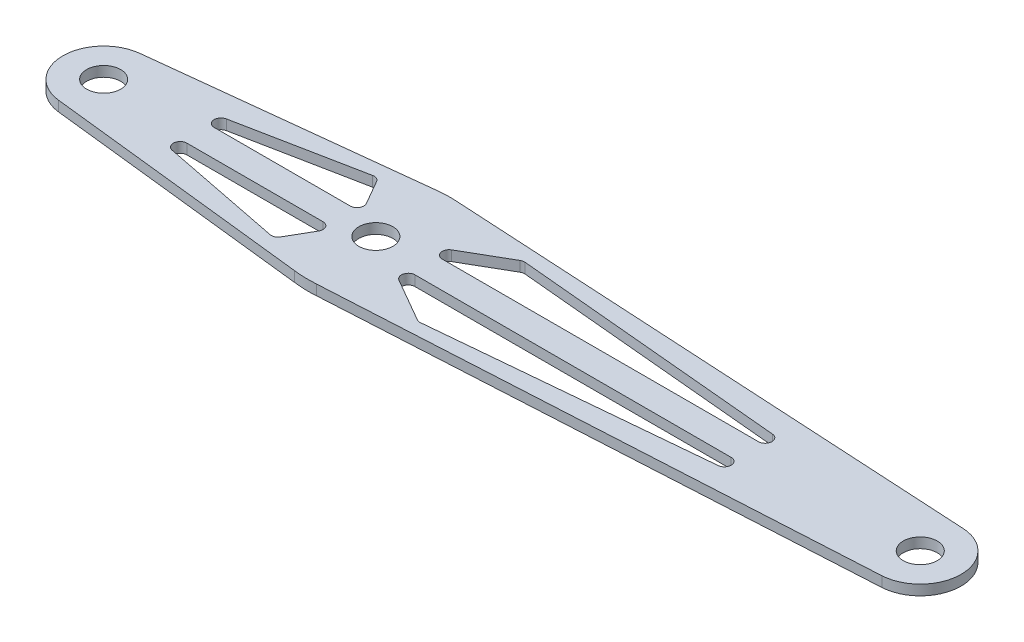
SolidWorks part; units mm, degrees
ref_plane "前视基准面" through (0, 0, 0) normal (0, 0, 1) x (1, 0, 0)
ref_plane "上视基准面" through (0, 0, 0) normal (0, 1, 0) x (1, 0, 0)
ref_plane "右视基准面" through (0, 0, 0) normal (1, 0, 0) x (0, 0, -1)
other "Configuration Table"
sketch "草图1" plane through (0, 0, 0) normal (0, 1, 0) x (1, 0, 0)
  line L0 (-96.1987, 0) -> (0, 0) construction
  line L1 (0, 0) -> (80, 0) construction
  line L2 (80, 0) -> (240, 0) construction
  line L3 (-1.3306, 11.926) -> (80, 21)
  line L4 (80, 21) -> (240.6725, 11.9811)
  line L5 (-1.3306, -11.926) -> (80, -21)
  line L6 (80, -21) -> (240.6725, -11.9811)
  circle A0 centre (0, 0) radius 5
  circle A1 centre (80, 0) radius 5
  circle A2 centre (240, 0) radius 5
  arc A3 (-1.3306, -11.926) -> (-1.3306, 11.926) centre (0, 0) cw
  arc A4 (240.6725, 11.9811) -> (240.6725, -11.9811) centre (240, 0) cw
  point P8 (80, 40.7077)
  point P13 (77.5983, -39.5312)
  point P16 (80, 51.4279)
  point P17 (80, -61.9462)
  point P18 (80, 26.739)
  dimension "D1" = 10
  dimension "D2" = 10
  dimension "D3" = 10
  dimension "D4" = 80
  dimension "D6" = 12
  dimension "D7" = 12
  dimension "D8" = 42
  dimension "D5" = 160
extrude "凸台-拉伸1" add sketch "草图1" along normal blind 3
fillet "圆角1" radius 40 2 edges at (80, 1.5, 21) (80, 1.5, -21) curvature continuous yes
sketch "草图2" plane through (0, 0, 0) normal (0, -1, 0) x (1, 0, 0)
  line L0 (240.8967, 15.9749) -> (83.5704, 24.8059) construction
  line L1 (76.2257, 24.6037) -> (-1.7741, 15.9013) construction
  line L2 (-1.7741, -15.9013) -> (76.2257, -24.6037) construction
  line L3 (83.5704, -24.8059) -> (240.8967, -15.9749) construction
  line L4 (240.6725, 11.9811) -> (83.3462, 20.8122)
  line L5 (76.6692, 20.6284) -> (-1.3306, 11.926)
  line L6 (-1.3306, -11.926) -> (76.6692, -20.6284)
  line L7 (83.3462, -20.8122) -> (240.6725, -11.9811)
  line L8 (240.6725, 11.9811) -> (83.3462, 20.8122) construction
  line L9 (76.6692, 20.6284) -> (-1.3306, 11.926) construction
  line L10 (-1.3306, -11.926) -> (76.6692, -20.6284) construction
  line L11 (83.3462, -20.8122) -> (240.6725, -11.9811) construction
  line L12 (83.122, -16.8185) -> (240.4483, -7.9874) construction
  line L13 (240.4483, 7.9874) -> (83.122, 16.8185) construction
  line L14 (77.1127, 16.6531) -> (-0.8871, 7.9507) construction
  line L15 (-0.8871, -7.9507) -> (77.1127, -16.6531) construction
  line L16 (-28.9871, 0) -> (305.3613, 0) construction
  line L17 (-28.9871, -4) -> (305.3613, -4) construction
  line L18 (-28.9871, 4) -> (305.3613, 4) construction
  line L19 (8.0623, 4) -> (65.3878, 15.3449)
  line L20 (65.3878, 15.3449) -> (71.9377, 4)
  line L21 (71.9377, 4) -> (8.0623, 4)
  line L22 (88.0623, 4) -> (107.8594, 15.4299)
  line L23 (107.8594, 15.4299) -> (231.9377, 4)
  line L24 (231.9377, 4) -> (88.0623, 4)
  line L25 (107.8594, -15.4299) -> (231.9377, -4)
  line L26 (88.0623, -4) -> (107.8594, -15.4299)
  line L27 (231.9377, -4) -> (88.0623, -4)
  line L28 (65.3878, -15.3449) -> (71.9377, -4)
  line L29 (8.0623, -4) -> (65.3878, -15.3449)
  line L30 (71.9377, -4) -> (8.0623, -4)
  circle A0 centre (240, 0) radius 5 construction
  circle A1 centre (80, 0) radius 5 construction
  arc A2 (-1.3306, 11.926) -> (-1.3306, -11.926) centre (0, 0) ccw
  arc A3 (240.6725, -11.9811) -> (240.6725, 11.9811) centre (240, 0) ccw
  arc A4 (-1.3306, 11.926) -> (-1.3306, -11.926) centre (0, 0) ccw construction
  arc A5 (240.6725, -11.9811) -> (240.6725, 11.9811) centre (240, 0) ccw construction
  circle A6 centre (0, 0) radius 5 construction
  circle A7 centre (240, 0) radius 5 construction
  circle A8 centre (80, 0) radius 5 construction
  circle A9 centre (0, 0) radius 5 construction
  arc A10 (-1.7741, 15.9013) -> (-1.7741, -15.9013) centre (0, 0) ccw construction
  circle A11 centre (240, 0) radius 9 construction
  circle A12 centre (80, 0) radius 9 construction
  circle A13 centre (0, 0) radius 9 construction
  arc A14 (240.4483, -7.9874) -> (240.4483, 7.9874) centre (240, 0) ccw construction
  arc A15 (-0.8871, 7.9507) -> (-0.8871, -7.9507) centre (0, 0) ccw construction
  arc A16 (240.8967, -15.9749) -> (240.8967, 15.9749) centre (240, 0) ccw construction
  spline S0 degree 1 poles (83.5704, 24.8059) (76.2257, 24.6037) knots 0 0 1 1 construction
  spline S1 degree 1 poles (76.2257, -24.6037) (83.5704, -24.8059) knots 0 0 1 1 construction
  spline S2 degree 2 poles (3072.0697, -237.9003) (127.5725, 19.5203) (81.6761, 20.8903) (80.7944, 20.9167) (80.0042, 20.895) (79.2143, 20.8733) (78.3339, 20.7984) (32.6608, 16.9155) (-2893.3663, -402.0343) knots -19.097283 -19.097283 -19.097283 0.25 0.25 0.5 0.5 0.75 0.75 20.066224 20.066224 20.066224 only from (83.3462, 20.8122) to (76.6692, 20.6284)
  spline S3 degree 2 poles (-2893.2975, 402.0989) (32.5809, -16.9056) (78.3325, -20.7983) (79.2114, -20.8731) (80.0016, -20.8949) (80.7914, -20.9167) (81.6746, -20.8904) (127.4922, -19.5258) (3072.1349, 237.8321) knots -19.097283 -19.097283 -19.097283 0.25 0.25 0.5 0.5 0.75 0.75 20.066224 20.066224 20.066224 only from (76.6692, -20.6284) to (83.3462, -20.8122)
  spline S4 degree 2 poles (83.3462, 20.8122) (82.2692, 20.8726) (81.6761, 20.8903) (80.7944, 20.9167) (80.0042, 20.895) (79.2143, 20.8733) (78.3339, 20.7984) (77.7428, 20.7482) (76.6692, 20.6284) knots 0 0 0 0.25 0.25 0.5 0.5 0.75 0.75 1 1 1 construction
  spline S5 degree 2 poles (76.6692, -20.6284) (77.7413, -20.748) (78.3325, -20.7983) (79.2114, -20.8731) (80.0016, -20.8949) (80.7914, -20.9167) (81.6746, -20.8904) (82.2676, -20.8727) (83.3462, -20.8122) knots 0 0 0 0.25 0.25 0.5 0.5 0.75 0.75 1 1 1 construction
  spline S6 degree 2 poles (83.5704, 24.8059) (82.8804, 24.8447) (82.2083, 24.874) (81.9692, 24.883) (81.8077, 24.8883) (81.5481, 24.8953) (81.2475, 24.9013) (80.7068, 24.9067) (79.8943, 24.8971) (79.0822, 24.862) (78.5422, 24.827) (78.2421, 24.8045) (77.9828, 24.7832) (77.8219, 24.7689) (77.5834, 24.7468) (76.9134, 24.6805) (76.2257, 24.6037) knots 0 0 0 0.15625 0.203125 0.234375 0.265625 0.296875 0.34375 0.4375 0.5625 0.65625 0.703125 0.734375 0.765625 0.796875 0.84375 1 1 1 construction
  spline S7 degree 2 poles (76.2257, -24.6037) (76.9125, -24.6804) (77.5819, -24.7467) (77.8202, -24.7688) (77.9811, -24.783) (78.24, -24.8043) (78.5398, -24.8268) (79.0794, -24.8619) (79.8912, -24.897) (80.7039, -24.9067) (81.2451, -24.9014) (81.546, -24.8954) (81.806, -24.8884) (81.9675, -24.883) (82.2069, -24.8741) (82.8794, -24.8447) (83.5704, -24.8059) knots 0 0 0 0.15625 0.203125 0.234375 0.265625 0.296875 0.34375 0.4375 0.5625 0.65625 0.703125 0.734375 0.765625 0.796875 0.84375 1 1 1 construction
  spline S8 degree 1 poles (83.122, 16.8185) (77.1127, 16.6531) knots 0 0 1 1 construction
  spline S9 degree 2 poles (83.122, 16.8185) (82.7287, 16.8405) (82.1945, 16.867) (81.8809, 16.8807) (81.6863, 16.888) (81.5677, 16.8919) (81.3613, 16.8975) (81.1273, 16.9021) (80.7114, 16.9062) (80.1138, 16.8991) (79.5172, 16.8734) (79.1018, 16.8465) (78.868, 16.8289) (78.6617, 16.812) (78.5437, 16.8015) (78.3498, 16.7836) (78.0372, 16.7527) (77.5048, 16.6968) (77.1127, 16.6531) knots 0 0 0 0.09375 0.15625 0.203125 0.234375 0.265625 0.296875 0.34375 0.4375 0.5625 0.65625 0.703125 0.734375 0.765625 0.796875 0.84375 0.90625 1 1 1 construction
  spline S10 degree 1 poles (77.1127, -16.6531) (83.122, -16.8185) knots 0 0 1 1 construction
  spline S11 degree 2 poles (77.1127, -16.6531) (77.5042, -16.6967) (78.0361, -16.7525) (78.3485, -16.7834) (78.5424, -16.8014) (78.6606, -16.8119) (78.8664, -16.8288) (79.0999, -16.8463) (79.5148, -16.8733) (80.112, -16.8991) (80.7091, -16.9062) (81.1254, -16.9022) (81.3598, -16.8975) (81.5666, -16.8919) (81.685, -16.888) (81.8796, -16.8807) (82.1934, -16.8671) (82.7282, -16.8406) (83.122, -16.8185) knots 0 0 0 0.09375 0.15625 0.203125 0.234375 0.265625 0.296875 0.34375 0.4375 0.5625 0.65625 0.703125 0.734375 0.765625 0.796875 0.84375 0.90625 1 1 1 construction
  point P55 (113.2075, 15.3449)
  point P60 (111.2291, 15.3449)
  point P61 (0, 0)
  point P62 (107.8594, 15.3449)
  point P63 (0, 0)
  dimension "D2" = 4
  dimension "D3" = 4
  dimension "D6" = 4
  dimension "D4" = 4
  dimension "D8" = 60
  dimension "D9" = 30
  dimension "D1" = 0
  dimension "D5" = 4
  dimension "D7" = 4
extrude "切除-拉伸1" cut sketch "草图2" against normal up to surface (3 mm away) up to face at (99.9216, 3, -0.0069)
fillet "圆角2" radius 2 12 edges at (65.3878, 1.5, -15.3449) (71.9377, 1.5, -4) (71.9377, 1.5, 4) (8.0623, 1.5, 4) (8.0623, 1.5, -4) (65.3878, 1.5, 15.3449) (107.8594, 1.5, -15.4299) (88.0623, 1.5, -4) (88.0623, 1.5, 4) (107.8594, 1.5, 15.4299) (231.9377, 1.5, -4) (231.9377, 1.5, 4)
